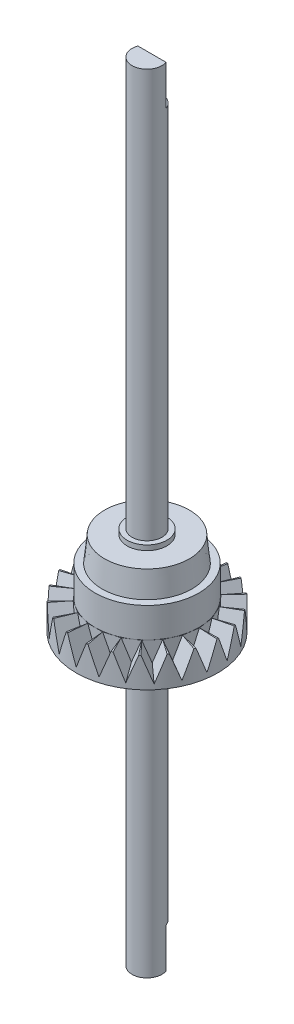
SolidWorks part; units mm, degrees
ref_plane "Ön Düzlem" through (0, 0, 0) normal (0, 0, 1) x (1, 0, 0)
ref_plane "Üst Düzlem" through (0, 0, 0) normal (0, 1, 0) x (1, 0, 0)
ref_plane "Sağ Düzlem" through (0, 0, 0) normal (1, 0, 0) x (0, 0, -1)
sketch "Sketch2" plane through (0, 0, 0) normal (0, 1, 0) x (1, 0, 0)
  circle A0 centre (0, 0) radius 1.5
  dimension "D1" = 3
extrude "Boss-Extrude1" add sketch "Sketch2" along normal blind 27
sketch "Sketch3" plane through (0, 27, 0) normal (0, 1, 0) x (1, 0, 0)
  circle A0 centre (0, 0) radius 2.5
  dimension "D1" = 5
extrude "Boss-Extrude2" add sketch "Sketch3" along normal blind 2 separate body
sketch "Sketch4" plane through (0, 29, 0) normal (0, 1, 0) x (1, 0, 0)
  circle A0 centre (0, 0) radius 7.1
  dimension "D1" = 14.2
extrude "Boss-Extrude3" add sketch "Sketch4" along normal blind 3
sketch "Sketch5" plane through (0, 32, 0) normal (0, 1, 0) x (1, 0, 0)
  circle A1 centre (0, 0) radius 5.2
  dimension "D1" = 10.4
extrude "Boss-Extrude4" add sketch "Sketch5" along normal blind 3 separate body
sketch "Sketch6" plane through (0, 35, 0) normal (0, 1, 0) x (1, 0, 0)
  circle A0 centre (0, 0) radius 4.5
  dimension "D1" = 9
ref_plane "Plane2" through (0, 37.5, 0) normal (0, 1, 0) x (1, 0, 0)
sketch "Sketch7" plane through (0, 37.5, 0) normal (0, 1, 0) x (1, 0, 0)
  circle A0 centre (0, 0) radius 4.25
  dimension "D1" = 8.5
loft "Loft1" add profiles "Sketch6", "Sketch7" connector at (-3.2881, 35, 3.0722) connector at (-2.6531, 37.5, 3.3202)
sketch "Sketch8" plane through (0, 37.5, 0) normal (0, 1, 0) x (1, 0, 0)
  circle A0 centre (0, 0) radius 2
  dimension "D1" = 4
extrude "Boss-Extrude5" add sketch "Sketch8" along normal blind 0.5
sketch "Sketch9" plane through (0, 38, 0) normal (0, 1, 0) x (1, 0, 0)
  circle A0 centre (0, 0) radius 1.5
  dimension "D1" = 3
extrude "Boss-Extrude6" add sketch "Sketch9" along normal blind 41
sketch "Sketch10" plane through (0, 0, 0) normal (0, 1, 0) x (1, 0, 0)
  line L0 (-1.4142, 0.5) -> (1.4142, 0.5)
  line L1 (0, 1.5) -> (0, 0.5) construction
  arc A0 (1.4142, 0.5) -> (-1.4142, 0.5) centre (0, 0) ccw
  dimension "D1" = 3
  dimension "D2" = 1
extrude "Cut-Extrude1" cut sketch "Sketch10" along normal blind 4
sketch "Sketch11" plane through (0, 79, 0) normal (0, 1, 0) x (1, 0, 0)
  line L0 (-1.4142, 0.5) -> (1.4142, 0.5)
  line L1 (0, 0.5) -> (0, 1.5) construction
  arc A0 (1.4142, 0.5) -> (-1.4142, 0.5) centre (0, 0) ccw
  dimension "D1" = 3
  dimension "D2" = 1
extrude "Cut-Extrude2" cut sketch "Sketch11" against normal blind 4
ref_plane "Plane3" through (0, 0, 7.1) normal (0, 0, 1) x (1, 0, 0)
sketch "Sketch12" plane through (0, 0, 7.1) normal (0, 0, 1) x (1, 0, 0)
  line L0 (0, 29.5) -> (-0.75, 31.5)
  line L2 (0.75, 31.5) -> (0, 29.5)
  line L3 (-0.75, 31.5) -> (-0.9375, 32)
  line L4 (-2.5, 29) -> (2.5, 29) construction
  line L5 (7.1, 32) -> (-7.1, 32) construction
  line L7 (-7.1, 29) -> (7.1, 29) construction
  line L8 (0.75, 31.5) -> (0.9375, 32)
  line L9 (-0.9375, 32) -> (0.9375, 32)
  dimension "D1" = 2.5
  dimension "D2" = 0.5
  dimension "D3" = 1.5
ref_plane "Plane4" through (0, 0, 5.2) normal (0, 0, 1) x (1, 0, 0)
sketch "Sketch13" plane through (0, 0, 5.2) normal (0, 0, 1) x (1, 0, 0)
  line L1 (0, 29.5) -> (-0.75, 31.5) construction
  line L2 (0.75, 31.5) -> (0, 29.5) construction
  line L3 (-0.75, 31.5) -> (0.75, 31.5) construction
  line L4 (0, 29.5) -> (-0.75, 31.5) construction
  line L5 (0.75, 31.5) -> (0, 29.5) construction
  line L6 (0, 30) -> (-0.75, 32)
  line L7 (-0.75, 32) -> (0.75, 32)
  line L8 (0.75, 32) -> (0, 30)
  line L10 (7.1, 32) -> (-7.1, 32) construction
  dimension "D1" = 2
loft "Cut-Loft8" cut profiles "Sketch12", "Sketch13" connector at (0, 29.5, 7.1) connector at (0, 30, 5.2)
pattern_circular "CirPattern2" count 22 over 360 about axis through (0, 32, 0) along (0, -1, 0) of "Cut-Loft8"
